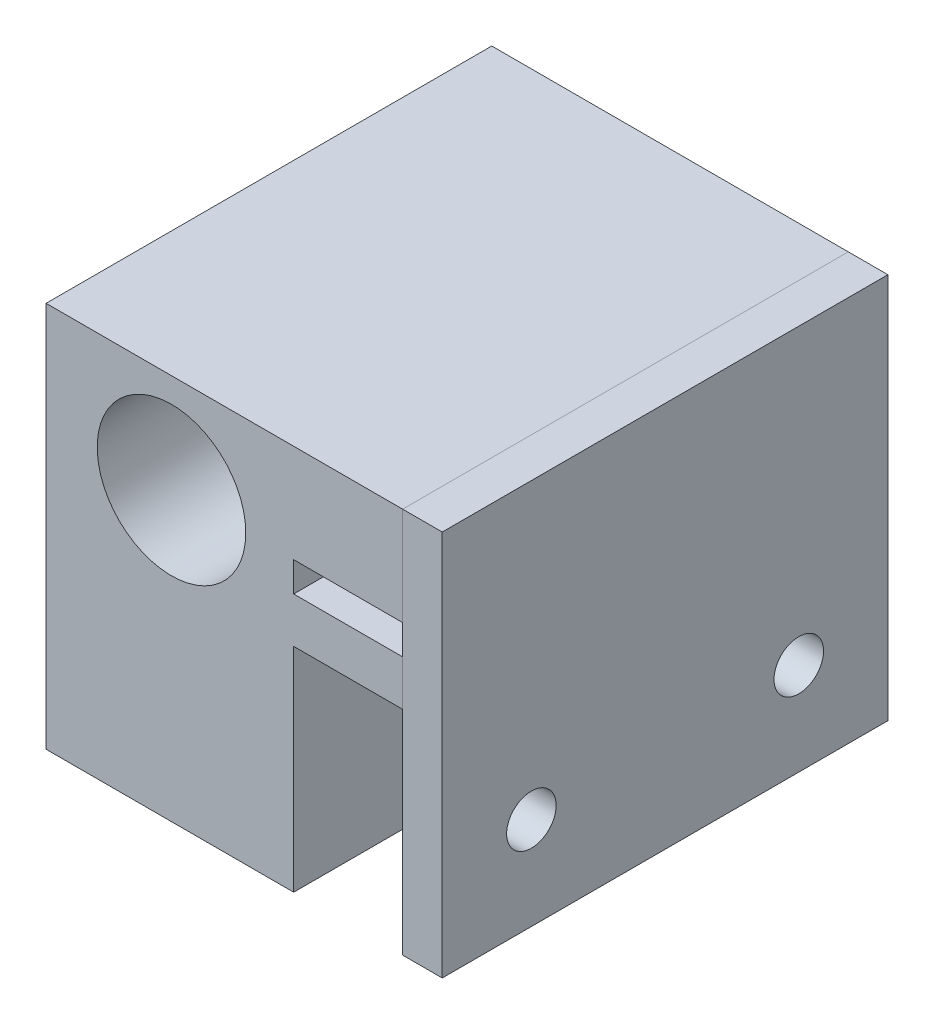
SolidWorks part; units mm, degrees
ref_plane "Front Plane" through (0, 0, 0) normal (0, 0, 1) x (1, 0, 0)
ref_plane "Top Plane" through (0, 0, 0) normal (0, 1, 0) x (1, 0, 0)
ref_plane "Right Plane" through (0, 0, 0) normal (1, 0, 0) x (0, 0, -1)
sketch "Sketch1" plane through (0, 0, 0) normal (0, 0, 1) x (1, 0, 0)
  line L5 (20, 29) -> (-20, 29)
  line L6 (20, 29) -> (20, -10)
  line L7 (20, -10) -> (-20, -10)
  line L8 (-20, 29) -> (-20, -10)
  line L9 (20, 29) -> (-20, -10) construction
  line L10 (20, -10) -> (-20, 29) construction
  circle A0 centre (-7.34, 19) radius 7.5
  point P0 (0, 9.5)
  dimension "D3" = 15
  dimension "D1" = 40
  dimension "D2" = 39
  dimension "D4" = 10
  dimension "D5" = 27.34
extrude "Boss-Extrude1" add sketch "Sketch1" against normal blind 45
sketch "Sketch3" plane through (0, -10, 0) normal (0, -1, 0) x (1, 0, 0)
  line L0 (-7.34, -0.349) -> (-7.34, -3.737) construction
  line L1 (-20, -45) -> (20, -45) construction
  line L2 (-7.34, 0) -> (-7.34, -45) construction
  line L3 (-20, 0) -> (20, 0) construction
  line L5 (-14.84, -0.349) -> (0.16, -0.349) construction
  circle A0 centre (-7.34, -11.25) radius 4
  circle A1 centre (-7.34, -33.75) radius 4
  point P5 (13.75, 0)
  dimension "D5" = 8
  dimension "D1" = 11.25
extrude "Cut-Extrude1" cut sketch "Sketch3" against normal blind 17
sketch "Sketch5" plane through (0, 0, -45) normal (0, 0, -1) x (-1, 0, 0)
  line L0 (-5, -10) -> (-5, 11.5)
  line L1 (20, -10) -> (-20, -10) construction
  line L3 (-16, 11.5) -> (-16, -10)
  line L4 (-16, -10) -> (-5, -10)
  line L5 (-20, -10) -> (-20, 29) construction
  line L7 (53, 9) -> (-447, 9) construction
  line L9 (-16, 19) -> (-5, 19) construction
  line L11 (-447, 19) -> (53, 19) construction
  line L12 (-16, 11.5) -> (-5, 11.5)
  line L13 (-16, 16.08) -> (-5, 16.08)
  line L14 (-16, 16.08) -> (-16, 19.08)
  line L15 (-16, 19.08) -> (-5, 19.08)
  line L16 (-5, 19.08) -> (-5, 16.08)
  dimension "D1" = 25
  dimension "D2" = 4
  dimension "D3" = 2.5
  dimension "D4" = 7.08
  dimension "D5" = 3
extrude "Cut-Extrude3" cut sketch "Sketch5" against normal through all
sketch "Sketch6" plane through (20, 0, 0) normal (1, 0, 0) x (0, 0, -1)
  line L1 (45, -10) -> (45, 29) construction
  line L2 (0, -10) -> (0, 29) construction
  line L6 (-195.0439, 9) -> (224.9561, 9) construction
  circle A0 centre (36, -0.65) radius 2.5
  circle A3 centre (9, -0.65) radius 2.5
  dimension "D2" = 5
  dimension "D3" = 9
  dimension "D4" = 9
  dimension "D1" = 9.65
extrude "Cut-Extrude4" cut sketch "Sketch6" against normal up to surface (4 mm away) up to face at (16, 0.75, -22.5)
ref_plane "Plane1" through (16, 0, 0) normal (-1, 0, 0) x (0, 0, 1)
split "Split1" trim tools "Plane1" bodies to split 105 resulting bodies 106 107
